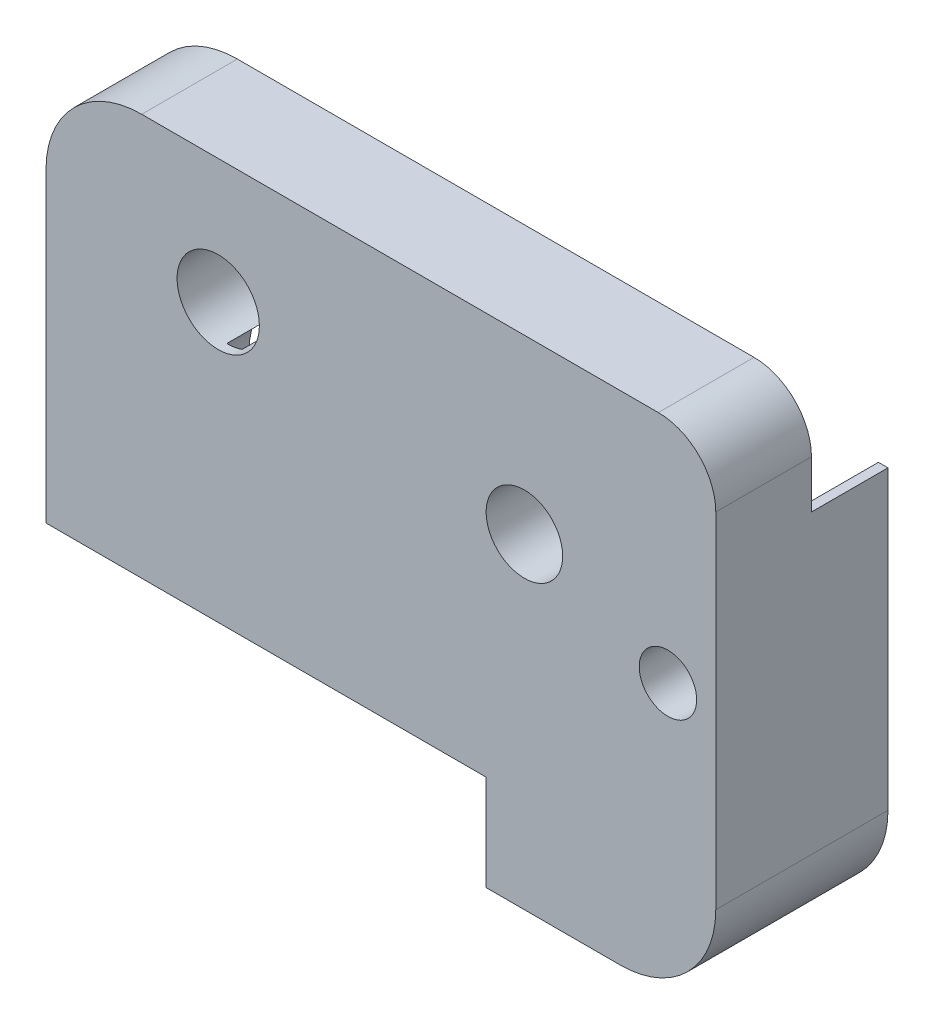
SolidWorks part; units mm, degrees
ref_plane "Front" through (0, 0, 0) normal (0, 0, 1) x (1, 0, 0)
ref_plane "Top" through (0, 0, 0) normal (0, 1, 0) x (1, 0, 0)
ref_plane "Right" through (0, 0, 0) normal (1, 0, 0) x (0, 0, -1)
sketch "Sketch1" plane through (0, 0, 0) normal (0, 0, 1) x (1, 0, 0)
  line L1 (-15, 6.5) -> (8, 6.5)
  line L2 (-15, 6.5) -> (-15, -14.5)
  line L3 (-15, -14.5) -> (8, -14.5)
  line L4 (8, 6.5) -> (8, -14.5)
  dimension "D1" = 15
  dimension "D2" = 14.5
  dimension "D3" = 6.5
  dimension "D4" = 8
extrude "Extrude1" add sketch "Sketch1" along normal blind 5
sketch "Sketch2" plane through (0, 0, 5) normal (0, 0, 1) x (1, 0, 0)
  circle A0 centre (-6, 0) radius 2.15
  dimension "D1" = 4.3
  dimension "D2" = 6
extrude "Extrude2" cut sketch "Sketch2" against normal blind 4.3
sketch "Sketch3" plane through (0, 0, 0) normal (0, 0, -1) x (-1, 0, 0)
  line L1 (15, -14.5) -> (-8, -14.5) construction
  line L2 (-8, -14.5) -> (-8, 6.5) construction
  circle A0 centre (4.9, -6.5) radius 4.5
  dimension "D1" = 9
  dimension "D3" = 8
  dimension "D2" = 12.9
extrude "Extrude3" cut sketch "Sketch3" against normal blind 4.5
sketch "Sketch4" plane through (0, -14.5, 0) normal (0, -1, 0) x (1, 0, 0)
  line L0 (8, 5) -> (8, 0) construction
  line L1 (-15, 5) -> (-15, 0) construction
  line L2 (-15, 0) -> (8, 0) construction
  circle A0 centre (-12, 2.5) radius 1.25
  circle A1 centre (1.4, 2.5) radius 1.25
  dimension "D1" = 2.5
  dimension "D2" = 2.5
  dimension "D4" = 3
  dimension "D5" = 2.5
  dimension "D6" = 2.5
  dimension "D3" = 6.6
extrude "Extrude4" cut sketch "Sketch4" against normal blind 8
cosmetic thread "Hole Thread1" parameters "D1"=6, "D2"=3
cosmetic thread "Hole Thread2" parameters "D1"=6, "D2"=3
sketch "Sketch7" plane through (0, 0, 5) normal (0, 0, 1) x (1, 0, 0)
  line L0 (-15, -14.5) -> (8, -14.5) construction
  line L1 (8, 6.5) -> (20, 6.5)
  line L2 (8, 6.5) -> (8, -19.5)
  line L3 (8, -19.5) -> (20, -19.5)
  line L4 (20, 6.5) -> (20, -19.5)
  dimension "D1" = 12
  dimension "D2" = 5
extrude "Extrude6" add sketch "Sketch7" against normal up to surface (5 mm away) up to face at (-9.4, -6.5, 0)
sketch "Sketch9" plane through (0, 0, 5) normal (0, 0, 1) x (1, 0, 0)
  line L0 (20, -19.5) -> (20, 6.5) construction
  line L3 (-15, -14.5) -> (8, -14.5) construction
  circle A0 centre (17.5, -5.5) radius 1.5
  dimension "D1" = 3
  dimension "D3" = 9
  dimension "D2" = 2.5
extrude "Extrude8" cut sketch "Sketch9" against normal up to surface (5 mm away) up to face at (-9.4, -6.5, 0)
sketch "Sketch8" plane through (0, 0, 5) normal (0, 0, 1) x (1, 0, 0)
  line L0 (20, -19.5) -> (20, 6.5) construction
  line L1 (20, 6.5) -> (-15, 6.5) construction
  circle A0 centre (10, -2.5) radius 2
  dimension "D1" = 4
  dimension "D3" = 9
  dimension "D2" = 10
extrude "Extrude7" cut sketch "Sketch8" against normal blind 4
fillet "Fillet2" radius 3 2 edges at (20, -19.5, 2.5) (20, 6.5, 2.5)
hole_wizard "M3 Tapped Hole1" positions "3DSketch1" profile "Sketch10" tap size "M3" standard "DIN"
sketch3d "3DSketch1"
  line L0 (-12, -6.5, 2.5) -> (-12, -14.5, 2.5) construction
  line L1 (1.4, -6.5, 2.5) -> (1.4, -14.5, 2.5) construction
  point P0 (-12, -14.5, 2.5)
  point P4 (1.4, -14.5, 2.5)
sketch "Sketch10" plane through (-12, -14.5, 2.5) normal (1, 0, 0) x (0, 0, -1)
  line L0 (0, 0) -> (0, 8.7511)
  line L1 (0, 8.7511) -> (1.25, 8)
  line L2 (1.25, 8) -> (1.25, 0)
  line L5 (1.25, 0) -> (0, 0)
  line L10 (0, 8.7511) -> (-1.25, 8) construction
  line L11 (0, -6.35) -> (0, 107.95) construction
  dimension "Tap Drill Dia." = 2.5
  dimension "Tap Drill Depth" = 8
  dimension "Drill Angle" = 118
sketch "Sketch11" plane through (0, 0, 0) normal (0, 0, -1) x (-1, 0, 0)
  line L0 (-8, -19.5) -> (-20, -19.5)
  line L1 (-20, -19.5) -> (-20, 1)
  line L2 (-20, 3.5) -> (-20, -16.5) construction
  line L3 (-20, 1) -> (-18.1, 1)
  line L4 (-18.1, 1) -> (-2, -11.07)
  line L5 (-2, -11.07) -> (-2, -14.5)
  line L6 (15, -14.5) -> (-8, -14.5) construction
  line L7 (-2, -14.5) -> (-8, -14.5)
  line L8 (-8, -14.5) -> (-8, -19.5)
  dimension "D1" = 18
  dimension "D2" = 1.9
  dimension "D3" = 8.43
  dimension "D4" = 20.5
extrude "Extrude9" add sketch "Sketch11" along normal blind 4
fillet "Fillet1" radius 5 2 edges at (-15, 6.5, 2.5) (20, -19.5, -2)
sketch "Sketch12" plane through (0, 0, -4) normal (0, 0, -1) x (-1, 0, 0)
  line L0 (-19.5, 1) -> (-19.5, -7.5)
  line L1 (-18.1, 1) -> (-20, 1) construction
  line L2 (-19.5, -7.5) -> (-15.5, -7.5)
  line L3 (-15.5, -7.5) -> (-15.5, -0.9492)
  line L4 (-2, -11.07) -> (-18.1, 1) construction
  line L5 (-15.5, -0.9492) -> (-18.1, 1)
  line L6 (-18.1, 1) -> (-19.5, 1)
  line L7 (-20, 1) -> (-20, -14.5) construction
  dimension "D1" = 4
  dimension "D2" = 0.5
  dimension "D3" = 8.5
extrude "Extrude10" cut sketch "Sketch12" against normal up to surface (4 mm away) up to face at (-9.4, -6.5, 0)
fillet "Fillet3" radius 2 2 edges at (15.5, -7.5, -2) (19.5, -7.5, -2)
